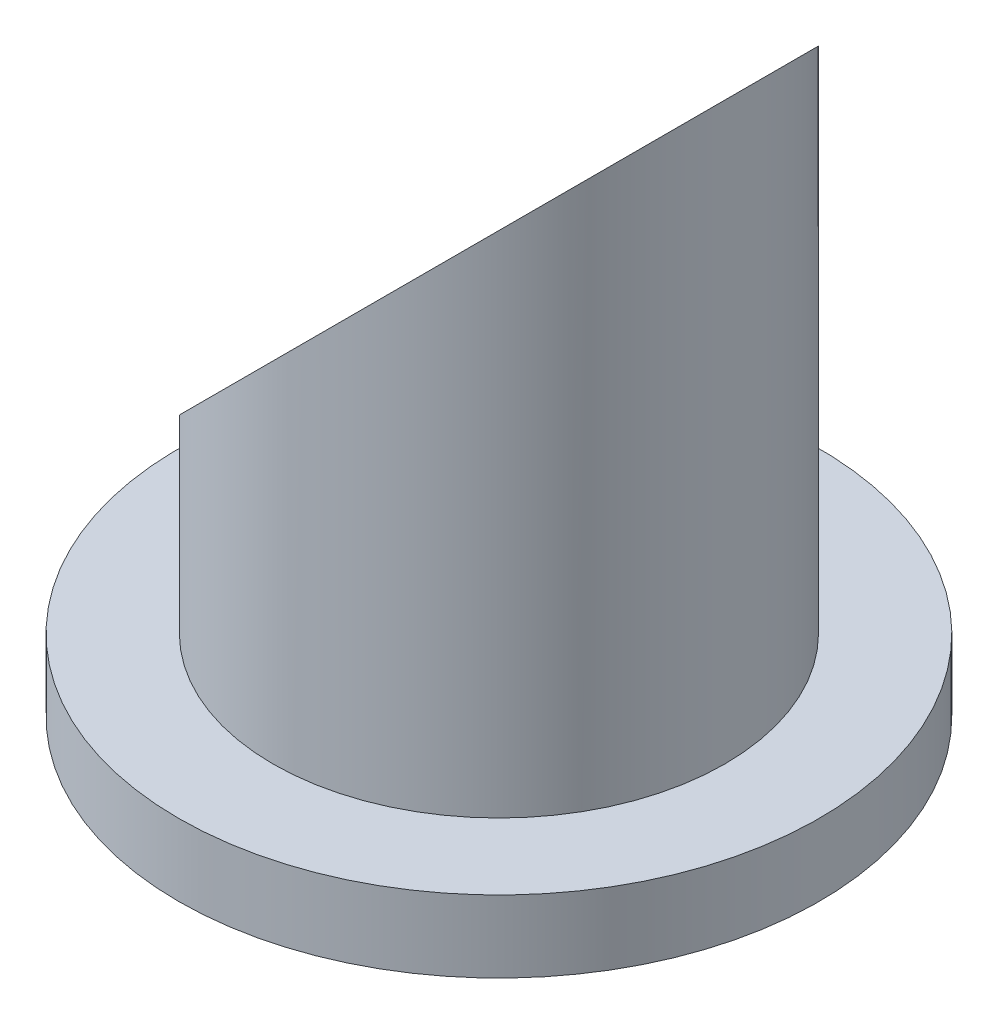
SolidWorks part; units mm, degrees
material "PTFE (general)"
ref_plane "Front Plane" through (0, 0, 0) normal (0, 0, 1) x (1, 0, 0)
ref_plane "Top Plane" through (0, 0, 0) normal (0, 1, 0) x (1, 0, 0)
ref_plane "Right Plane" through (0, 0, 0) normal (1, 0, 0) x (0, 0, -1)
sketch "Sketch1" plane through (0, 0, 0) normal (0, 1, 0) x (1, 0, 0)
  circle A0 centre (0, 0) radius 8.9
  dimension "D1" = 17.8
extrude "Boss-Extrude1" add sketch "Sketch1" along normal blind 2
sketch "Sketch2" plane through (0, 2, 0) normal (0, 1, 0) x (1, 0, 0)
  circle A0 centre (0, 0) radius 6.28
  dimension "D1" = 12.56
extrude "Boss-Extrude2" add sketch "Sketch2" along normal blind 20
sketch "Sketch3" plane through (0, 0, 0) normal (0, 0, 1) x (1, 0, 0)
  line L0 (-6.28, 5.42) -> (6.28, 17.98)
  line L2 (8.9, 2) -> (-8.9, 2) construction
  line L4 (-6.28, 5.42) -> (-6.28, 28.7719)
  line L5 (-6.28, 28.7719) -> (6.28, 28.7719)
  line L6 (6.28, 17.98) -> (6.28, 28.7719)
  point P2 (0, 11.7)
  dimension "D1" = 12.56
  dimension "D2" = 45
  dimension "D3" = 12.56
  dimension "D4" = 6.28
  dimension "D5" = 9.7
extrude "Cut-Extrude1" cut sketch "Sketch3" against normal through all both and the other way through all contours L0 L6 L5 L4 region at (-0.77, 19.8509, 0)
